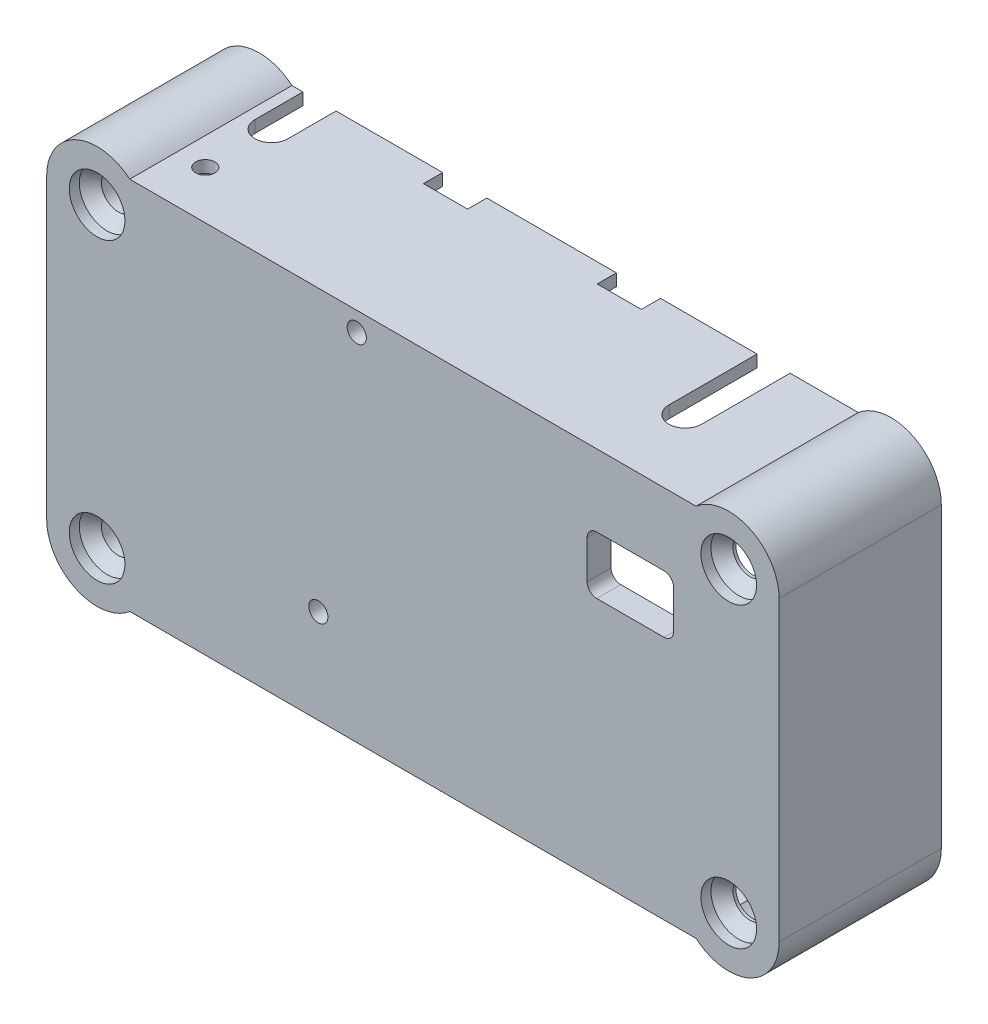
SolidWorks part; units mm, degrees
ref_plane "Front Plane" through (0, 0, 0) normal (0, 0, 1) x (1, 0, 0)
ref_plane "Top Plane" through (0, 0, 0) normal (0, 1, 0) x (1, 0, 0)
ref_plane "Right Plane" through (0, 0, 0) normal (1, 0, 0) x (0, 0, -1)
sketch "Sketch1" plane through (0, 0, 0) normal (0, 0, 1) x (1, 0, 0)
  line L0 (-29.7106, 19.8451) -> (30.4992, 19.8451)
  line L1 (-36.2557, 17.3451) -> (-36.2557, -13.6549)
  line L2 (-29.7106, -16.1549) -> (30.4992, -16.1549)
  line L3 (37.0443, 17.3451) -> (37.0443, -13.6549)
  circle A1 centre (-32.5057, 17.3451) radius 3.75
  arc A2 (-29.7106, 19.8451) -> (-36.2557, 17.3451) centre (-32.5057, 17.3451) ccw construction
  circle A3 centre (-32.5057, 17.3451) radius 1.75
  circle A4 centre (-32.5057, 17.3451) radius 1.75 construction
  circle A8 centre (-32.5057, -13.6549) radius 1.75
  circle A9 centre (-32.5057, -13.6549) radius 1.75 construction
  circle A10 centre (-32.5057, -13.6549) radius 3.75
  arc A11 (-36.2557, -13.6549) -> (-29.7106, -16.1549) centre (-32.5057, -13.6549) ccw construction
  circle A12 centre (33.2943, 17.3451) radius 3.75
  circle A14 centre (33.2943, 17.3451) radius 1.75
  circle A16 centre (33.2943, -13.6549) radius 3.75
  circle A18 centre (33.2943, -13.6549) radius 1.75
  circle A20 centre (33.2943, -13.6549) radius 1.75 construction
  circle A21 centre (33.2943, 17.3451) radius 1.75 construction
  arc A22 (37.0443, 17.3451) -> (30.1222, 15.3451) centre (33.2943, 17.3451) ccw construction
extrude "Boss-Extrude1" add sketch "Sketch1" along normal blind 2.5 contours A16 L3 A12 L0 A1 L1 A10 L2 | A1 A3 | A10 A8 | A12 A14 | A16 A18 region at (0.3943, 1.8451, 0) region at (-29.1016, 18.6453, 0) region at (34.5945, 20.7492, 0) region at (-32.5057, -10.011, 0) region at (34.5945, -17.059, 0)
sketch "Sketch2" plane through (0, 0, 2.5) normal (0, 0, 1) x (1, 0, 0)
  line L0 (-37.7557, 17.3451) -> (-37.7557, -13.6549)
  line L1 (-29.1053, -17.6549) -> (29.8939, -17.6549)
  line L2 (38.5443, -13.6549) -> (38.5443, 17.3451)
  line L3 (29.8939, 21.3451) -> (-29.1053, 21.3451)
  line L4 (-29.7106, -16.1549) -> (30.4992, -16.1549)
  line L5 (37.0443, -13.6549) -> (37.0443, 17.3451)
  line L6 (30.4992, 19.8451) -> (-29.7106, 19.8451)
  line L7 (-36.2557, 17.3451) -> (-36.2557, -13.6549)
  line L8 (-29.7106, -16.1549) -> (30.4992, -16.1549)
  line L9 (37.0443, -13.6549) -> (37.0443, 17.3451)
  line L10 (30.4992, 19.8451) -> (-29.7106, 19.8451)
  line L11 (-36.2557, 17.3451) -> (-36.2557, -13.6549)
  arc A0 (-29.1053, 21.3451) -> (-37.7557, 17.3451) centre (-32.5057, 17.3451) ccw
  arc A1 (-37.7557, -13.6549) -> (-29.1053, -17.6549) centre (-32.5057, -13.6549) ccw
  arc A2 (29.8939, -17.6549) -> (38.5443, -13.6549) centre (33.2943, -13.6549) ccw
  arc A3 (38.5443, 17.3451) -> (29.8939, 21.3451) centre (33.2943, 17.3451) ccw
  arc A4 (30.4992, -16.1549) -> (37.0443, -13.6549) centre (33.2943, -13.6549) ccw
  arc A5 (37.0443, 17.3451) -> (30.4992, 19.8451) centre (33.2943, 17.3451) ccw
  arc A6 (-29.7106, 19.8451) -> (-36.2557, 17.3451) centre (-32.5057, 17.3451) ccw
  arc A7 (-36.2557, -13.6549) -> (-29.7106, -16.1549) centre (-32.5057, -13.6549) ccw
  arc A8 (30.4992, -16.1549) -> (37.0443, -13.6549) centre (33.2943, -13.6549) ccw
  arc A9 (37.0443, 17.3451) -> (30.4992, 19.8451) centre (33.2943, 17.3451) ccw
  arc A10 (-29.7106, 19.8451) -> (-36.2557, 17.3451) centre (-32.5057, 17.3451) ccw
  arc A11 (-36.2557, -13.6549) -> (-29.7106, -16.1549) centre (-32.5057, -13.6549) ccw
  dimension "D1" = 0
  dimension "D2" = 1.5
extrude "Boss-Extrude2" add sketch "Sketch2" against normal up to surface (2.5 mm away) up to face at (0.3943, 1.8451, 0)
sketch "Sketch3" plane through (0, 0, 0) normal (0, 0, -1) x (-1, 0, 0)
  line L1 (29.601, 20.0951) -> (-30.3896, 20.0951)
  line L2 (-37.2943, 17.3451) -> (-37.2943, -13.6549)
  line L3 (-30.3896, -16.4049) -> (29.601, -16.4049)
  line L4 (29.1053, 21.3451) -> (-29.8939, 21.3451)
  line L5 (-38.5443, 17.3451) -> (-38.5443, -13.6549)
  line L6 (-29.8939, -17.6549) -> (29.1053, -17.6549)
  line L7 (37.7557, -13.6549) -> (37.7557, 17.3451)
  line L8 (29.1053, 21.3451) -> (-29.8939, 21.3451)
  line L9 (-38.5443, 17.3451) -> (-38.5443, -13.6549)
  line L10 (-29.8939, -17.6549) -> (29.1053, -17.6549)
  line L11 (37.7557, -13.6549) -> (37.7557, 17.3451)
  line L12 (36.5057, -13.6549) -> (36.5057, 17.3451)
  arc A1 (-30.3896, 20.0951) -> (-37.2943, 17.3451) centre (-33.2943, 17.3451) ccw
  arc A2 (-37.2943, -13.6549) -> (-30.3896, -16.4049) centre (-33.2943, -13.6549) ccw
  arc A3 (29.601, -16.4049) -> (36.5057, -13.6549) centre (32.5057, -13.6549) ccw
  arc A4 (37.7557, 17.3451) -> (29.1053, 21.3451) centre (32.5057, 17.3451) ccw
  arc A5 (-29.8939, 21.3451) -> (-38.5443, 17.3451) centre (-33.2943, 17.3451) ccw
  arc A6 (-38.5443, -13.6549) -> (-29.8939, -17.6549) centre (-33.2943, -13.6549) ccw
  arc A7 (29.1053, -17.6549) -> (37.7557, -13.6549) centre (32.5057, -13.6549) ccw
  arc A8 (37.7557, 17.3451) -> (29.1053, 21.3451) centre (32.5057, 17.3451) ccw
  arc A9 (-29.8939, 21.3451) -> (-38.5443, 17.3451) centre (-33.2943, 17.3451) ccw
  arc A10 (-38.5443, -13.6549) -> (-29.8939, -17.6549) centre (-33.2943, -13.6549) ccw
  arc A11 (29.1053, -17.6549) -> (37.7557, -13.6549) centre (32.5057, -13.6549) ccw
  arc A12 (36.5057, 17.3451) -> (29.601, 20.0951) centre (32.5057, 17.3451) ccw
  dimension "D1" = 0
  dimension "D2" = 1.25
extrude "Boss-Extrude3" add sketch "Sketch3" along normal up to surface (14.4 mm away)
sketch "Sketch8" plane through (0, 0, 0) normal (0, 0, -1) x (-1, 0, 0)
  line L0 (37.7557, 17.3451) -> (37.7557, -13.6549)
  line L1 (29.1053, 21.3451) -> (29.1053, -17.6549)
  circle A0 centre (32.5057, 17.3451) radius 5.25
  arc A1 (37.7557, 17.3451) -> (29.1053, 21.3451) centre (32.5057, 17.3451) ccw construction
  circle A2 centre (32.5057, 17.3451) radius 1.75
  circle A3 centre (32.5057, 17.3451) radius 1.75 construction
  circle A4 centre (32.5057, -13.6549) radius 5.25
  arc A5 (29.1053, -17.6549) -> (37.7557, -13.6549) centre (32.5057, -13.6549) ccw construction
  circle A6 centre (32.5057, -13.6549) radius 1.75
  circle A7 centre (32.5057, -13.6549) radius 1.75 construction
  circle M3 centre (32.5057, 17.3451) radius 1.75
  circle M4 centre (32.5057, -13.6549) radius 1.75
  arc M5 (29.601, -16.4049) -> (36.5057, -13.6549) centre (32.5057, -13.6549) ccw
  line M6 (36.5057, -13.6549) -> (36.5057, 17.3451)
  arc M7 (36.5057, 17.3451) -> (29.601, 20.0951) centre (32.5057, 17.3451) ccw
  line M8 (29.601, 20.0951) -> (-30.3896, 20.0951)
  line M12 (-30.3896, -16.4049) -> (29.601, -16.4049)
extrude "Boss-Extrude4" add sketch "Sketch8" along normal up to surface (6.75 mm away) contours L1 A0 M6 M7 M8 M3 | A4 A0 L1 M6 | A4 L1 M6 M12 M5 M4 region at (-32.835, 1.8451, 0) region at (-32.9201, 12.2303, 0) region at (-36.3872, -11.9547, 0)
sketch "Sketch4" plane through (-37.7557, 0, 0) normal (-1, 0, 0) x (0, 0, 1)
  line L12 (-11.9, -11.8549) -> (-3.3, -11.8549)
  line L13 (-3.3, -11.8549) -> (-3.3, 1.2216)
  line L14 (-3.3, 1.2216) -> (-6.0107, 4.2451)
  line L15 (-6.0107, 4.2451) -> (-9.1893, 4.2451)
  line L16 (-9.1893, 4.2451) -> (-11.9, 1.2216)
  line L17 (-11.9, 1.2216) -> (-11.9, -11.8549)
  line L18 (-11.9, -11.8549) -> (-3.3, -11.8549)
  line L19 (-3.3, -11.8549) -> (-3.3, 1.2216)
  line L20 (-3.3, 1.2216) -> (-6.0107, 4.2451)
  line L21 (-6.0107, 4.2451) -> (-9.1893, 4.2451)
  line L22 (-9.1893, 4.2451) -> (-11.9, 1.2216)
  line L23 (-11.9, 1.2216) -> (-11.9, -11.8549)
  dimension "D1" = 0.2
extrude "Cut-Extrude1" cut sketch "Sketch4" against normal up to next
sketch "Sketch5" plane through (0, 21.3451, 0) normal (0, 1, 0) x (1, 0, 0)
  line L0 (-27.9607, 9.4) -> (-27.9607, 14.4)
  line L1 (-29.1053, 14.4) -> (29.8939, 14.4) construction
  line L2 (-24.5107, 9.4) -> (-24.5107, 14.4)
  line L3 (-24.5107, 14.4) -> (-27.9607, 14.4)
  line L4 (19.3445, 5.2047) -> (19.3445, 14.4)
  line L5 (22.7945, 5.2047) -> (22.7945, 14.4)
  circle A1 centre (21.0695, 5.2047) radius 1.725
  circle A2 centre (-26.2357, 9.4) radius 1.725
  circle A3 centre (-26.2357, 9.4) radius 1.725
  circle A4 centre (21.0695, 5.2047) radius 0.95 construction
  line M3 (29.8939, 14.4) -> (-29.1053, 14.4)
  dimension "D1" = 0.5
extrude "Cut-Extrude2" cut sketch "Sketch5" against normal up to next contours A3 | A3 L2 L0 M3 | A1 L5 L4 M3 | A1 region at (21.0695, 21.3451, -10.4703) region at (-26.2357, 21.3451, -12.5571) region at (-26.2357, 21.3451, -9.4) region at (21.0695, 21.3451, -5.2047)
sketch "Sketch6" plane through (0, 21.3451, 0) normal (0, 1, 0) x (1, 0, 0)
  line L0 (-26.2357, 7.675) -> (-26.2357, -2.5) construction
  line L1 (29.8939, -2.5) -> (-29.1053, -2.5) construction
  arc A0 (-27.9607, 9.4) -> (-24.5107, 9.4) centre (-26.2357, 9.4) ccw construction
  circle A1 centre (-26.2357, 2.5) radius 1
  dimension "D1" = 2
  dimension "D2" = 5
extrude "Cut-Extrude3" cut sketch "Sketch6" against normal through all
sketch "Sketch7" plane through (0, 0, 2.5) normal (0, 0, 1) x (1, 0, 0)
  line L1 (27.5443, 7.8451) -> (18.5443, 7.8451)
  line L2 (27.5443, 7.8451) -> (27.5443, 13.8451)
  line L3 (27.5443, 13.8451) -> (18.5443, 13.8451)
  line L4 (18.5443, 7.8451) -> (18.5443, 13.8451)
  line L6 (38.5443, -13.6549) -> (38.5443, 17.3451) construction
  line L7 (29.8939, 21.3451) -> (-29.1053, 21.3451) construction
  line L8 (-3.2057, 19.3451) -> (-3.2057, 21.3451) construction
  line L9 (-7.7057, 19.3451) -> (-7.7057, 21.3451) construction
  line L10 (-3.2057, 18.0451) -> (-3.2057, 19.8451) construction
  line L11 (-7.7057, 18.0451) -> (-7.7057, 19.8451) construction
  circle A0 centre (-9.4557, -7.8549) radius 1
  circle A1 centre (-5.4557, 19.3451) radius 2.25
  circle A2 centre (-9.4557, -7.8549) radius 0.875 construction
  circle A3 centre (-5.4557, 19.3451) radius 1
  dimension "D5" = 2
  dimension "D6" = 2
  dimension "D1" = 11
  dimension "D2" = 7.5
  dimension "D3" = 6
  dimension "D4" = 9
extrude "Cut-Extrude4" cut sketch "Sketch7" against normal up to next contours L4 L1 L2 L3 | A3 | A0 region at (23.0443, 10.8451, 2.5) region at (-9.4557, -7.8549, 2.5) region at (-5.4557, 19.3451, 2.5)
sketch "Sketch9" plane through (0, 0, 2.5) normal (0, 0, 1) x (1, 0, 0)
  circle A0 centre (-32.5057, 17.3451) radius 2.9
  circle A1 centre (33.2943, 17.3451) radius 2.9
  circle A2 centre (33.2943, -13.6549) radius 2.9
  circle A3 centre (-32.5057, -13.6549) radius 2.9
  dimension "D1" = 5.8
extrude "Cut-Extrude5" cut sketch "Sketch9" against normal blind 0.2
chamfer "Chamfer1" distance 2 angle 45 4 edges at (35.0443, -13.6549, 2.3) (35.0443, 17.3451, 2.3) (-30.7557, -13.6549, 2.3) (-30.7557, 17.3451, 2.3)
sketch "Sketch10" plane through (0, 21.3451, 0) normal (0, 1, 0) x (1, 0, 0)
  line L0 (-24.5107, 14.4) -> (19.3445, 14.4) construction
  line L1 (9.2943, 14.4) -> (4.6943, 14.4)
  line L2 (9.2943, 14.4) -> (9.2943, 12.4)
  line L3 (9.2943, 12.4) -> (4.6943, 12.4)
  line L4 (4.6943, 14.4) -> (4.6943, 12.4)
  line L5 (9.2943, 13.7) -> (9.2943, 11.9) construction
  line L6 (4.6943, 13.7) -> (4.6943, 11.9) construction
  line L7 (-8.8057, 13.7) -> (-8.8057, 11.9) construction
  line L8 (-8.8057, 14.4) -> (-13.4057, 14.4)
  line L9 (-8.8057, 14.4) -> (-8.8057, 12.4)
  line L10 (-8.8057, 12.4) -> (-13.4057, 12.4)
  line L11 (-13.4057, 14.4) -> (-13.4057, 12.4)
  line L12 (-13.4057, 13.7) -> (-13.4057, 11.9) construction
  dimension "D1" = 2
extrude "Cut-Extrude6" cut sketch "Sketch10" against normal through all
fillet "Fillet1" radius 1 4 edges at (27.5443, 13.8451, 1.25) (27.5443, 7.8451, 1.25) (18.5443, 7.8451, 1.25) (18.5443, 13.8451, 1.25)
sketch "Sketch11" plane through (0, 0, -3.3) normal (0, 0, -1) x (-1, 0, 0)
  line L0 (29.1053, -5.3166) -> (36.5057, -5.3166) construction
  line L1 (29.1053, 1.2216) -> (29.1053, -11.8549) construction
  line L2 (36.5057, -13.6549) -> (36.5057, 17.3451) construction
  line L3 (29.1053, 1.2216) -> (37.7557, 1.2216) construction
  line L4 (32.5555, 1.2216) -> (33.0555, 1.2216)
  line L5 (32.5555, 1.2216) -> (32.5555, -11.8549)
  line L6 (32.5555, -11.8549) -> (33.0555, -11.8549)
  line L7 (33.0555, 1.2216) -> (33.0555, -11.8549)
  line L8 (32.5555, 1.2216) -> (33.0555, -11.8549) construction
  line L9 (32.5555, -11.8549) -> (33.0555, 1.2216) construction
  point P6 (32.8055, -5.3166)
  dimension "D1" = 0.5
extrude "Boss-Extrude5" add sketch "Sketch11" along normal blind 0.25
